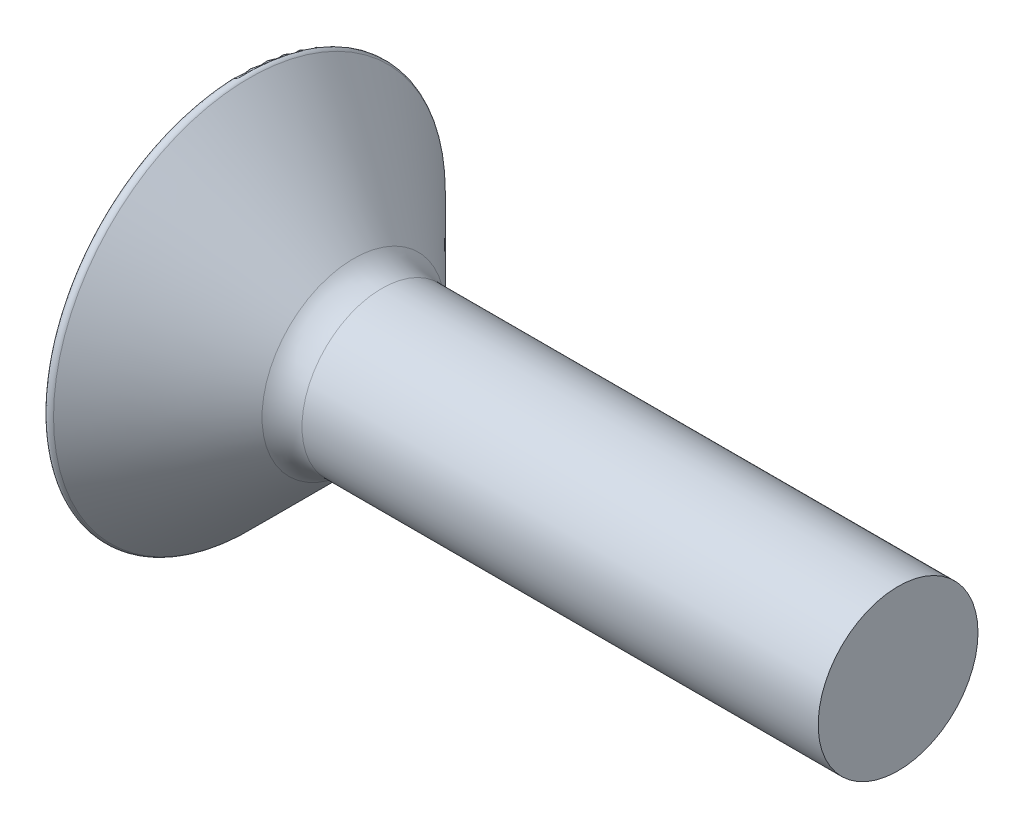
SolidWorks part; units mm, degrees
ref_plane "Front" through (0, 0, 0) normal (0, 0, 1) x (1, 0, 0)
ref_plane "Top" through (0, 0, 0) normal (0, 1, 0) x (1, 0, 0)
ref_plane "Right" through (0, 0, 0) normal (1, 0, 0) x (0, 0, -1)
ref_plane "Plane1" through (4.6, 0, 0) normal (1, 0, 0) x (0, 0, -1)
sketch "Sketch1" plane through (4.6, 0, 0) normal (1, 0, 0) x (0, 0, -1)
  circle A0 centre (0, 0) radius 3
extrude "BaseHead" add sketch "Sketch1" against normal blind 4.6 draft 45 draft outward yes
sketch "Sketch2" plane through (4.6, 0, 0) normal (1, 0, 0) x (0, 0, -1)
  circle A1 centre (0, 0) radius 3
extrude "BaseBody" add sketch "Sketch2" along normal blind 20
cosmetic thread "ThreadCosmetic1" [suppressed] parameters "D1"=18, "THD_MINOR"=5
dome "BaseTop" faces to dome 1 distance 1 reverse direction no elliptical dome no face at (0, 0, -7.6) parameters "f"=1
sketch "Sketch4" plane through (0, 0, 0) normal (1, 0, 0) x (0, 0, -1)
  line L1 (2.396, 0) -> (1.198, 2.075)
  line L2 (1.198, 2.075) -> (-1.198, 2.075)
  line L3 (-1.198, 2.075) -> (-2.396, 0)
  line L4 (-2.396, 0) -> (-1.198, -2.075)
  line L5 (-1.198, -2.075) -> (1.198, -2.075)
  line L6 (1.198, -2.075) -> (2.396, 0)
  circle A0 centre (0, 0) radius 2.075 construction
  dimension "B" = 4.15
extrude "Socket" cut sketch "Sketch4" along normal blind 2 and the other way blind 10
sketch "Sketch5" plane through (2, 0, 0) normal (-1, 0, 0) x (0, 0, 1)
  line L0 (2.396, 0) -> (1.198, -2.075) construction
  line L1 (1.198, 2.075) -> (2.396, 0) construction
  line L2 (1.198, -2.075) -> (-1.198, -2.075) construction
  line L3 (-1.198, -2.075) -> (-2.396, 0) construction
  line L4 (-2.396, 0) -> (-1.198, 2.075) construction
  line L5 (-1.198, 2.075) -> (1.198, 2.075) construction
  line L6 (2.396, 0) -> (1.198, -2.075)
  line L7 (1.198, 2.075) -> (2.396, 0)
  line L8 (1.198, -2.075) -> (-1.198, -2.075)
  line L9 (-1.198, -2.075) -> (-2.396, 0)
  line L10 (-2.396, 0) -> (-1.198, 2.075)
  line L11 (-1.198, 2.075) -> (1.198, 2.075)
extrude "Cut-Extrude2" cut sketch "Sketch5" against normal blind 5 draft 60
sketch "Sketch6" plane through (-30.7487, 13.2487, 0) normal (0, 0, 1) x (0, -1, 0)
  line L0 (13.2487, 89.8637) -> (13.2487, 24.8312) construction
  line L1 (10.6609, 35.7609) -> (10.2487, 35.3487)
  line L2 (-4.2513, 35.3487) -> (-4.2513, 45.3487)
  line L3 (-4.2513, 45.3487) -> (10.2487, 45.3487)
  line L4 (10.7487, 35.973) -> (10.7487, 44.0077)
  line L5 (10.2487, 35.3487) -> (5.6487, 30.7487) construction
  line L6 (10.2487, 45.3487) -> (10.7487, 44.0077)
  line L7 (10.2487, 35.3487) -> (-4.2513, 35.3487)
  line L8 (16.2487, 55.3487) -> (10.2487, 55.3487) construction
  arc A0 (10.7487, 35.973) -> (10.6609, 35.7609) centre (10.4487, 35.973) cw
  dimension "D3" = 0.3
  dimension "d1" = 5
  dimension "D2" = 15
  dimension "b" = 10
  dimension "x" = 1.341
fillet "HeadFillet" radius 0.2 1 edges at (0, 0, -7.6)
fillet "Fillet1" radius 1.5 1 edges at (4.6, 0, -3)
sketch "Sketch7" plane through (0, 0, 0) normal (0, 0, 1) x (1, 0, 0)
  line L0 (24.6, 2.567) -> (24.85, 3)
  line L1 (24.85, 3) -> (24.85, 3.5)
  line L2 (24.85, 3.5) -> (24.35, 3.5)
  line L3 (24.35, 3.5) -> (24.35, 3)
  line L4 (24.35, 3) -> (24.6, 2.567)
  line L5 (0, 0) -> (27.1886, 0) construction
  line L6 (24.6, -3) -> (24.6, 3) construction
  dimension "D1" = 0.5
  dimension "D2" = 6
revolve "Cut-Revolve10" [suppressed] cut sketch "Sketch7" angle 360 about L5
pattern_linear "LPattern10" [suppressed] count 30 spacing 0.6 along (-1, 0, 0) of bodies 106
equation "\"D1@Plane1\" = \"k@BaseHead\""
equation "\"D2@Sketch7\" = \"d@Sketch2\""
equation "\"D1@Sketch7\" =  ( \"d@Sketch2\" - \"THD_MINOR@ThreadCosmetic1\" )  / 2"
equation "\"D3@LPattern10\" = \"D1@Sketch7\" * 1.2"
equation "\"D1@LPattern10\" = \"D1@ThreadCosmetic1\" / \"D3@LPattern10\" "
